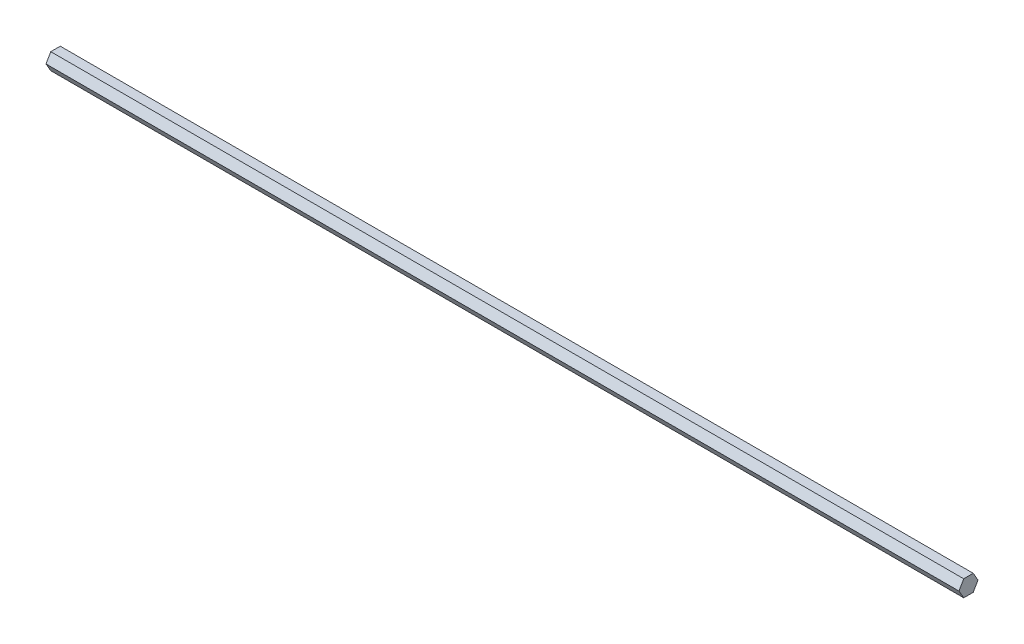
SolidWorks part; units mm, degrees
material "1060 Alloy"
ref_plane "Front Plane" through (0, 0, 0) normal (0, 0, 1) x (1, 0, 0)
ref_plane "Top Plane" through (0, 0, 0) normal (0, 1, 0) x (1, 0, 0)
ref_plane "Right Plane" through (0, 0, 0) normal (1, 0, 0) x (0, 0, -1)
sketch "Sketch1" plane through (0, 0, 0) normal (1, 0, 0) x (0, 0, -1)
  line L1 (7.3323, 0) -> (3.6662, 6.35)
  line L2 (3.6662, 6.35) -> (-3.6662, 6.35)
  line L3 (-3.6662, 6.35) -> (-7.3323, 0)
  line L4 (-7.3323, 0) -> (-3.6662, -6.35)
  line L5 (-3.6662, -6.35) -> (3.6662, -6.35)
  line L6 (3.6662, -6.35) -> (7.3323, 0)
  circle A0 centre (0, 0) radius 6.35 construction
  dimension "D1" = 12.7
extrude "Boss-Extrude1" add sketch "Sketch1" along normal blind 703.072
